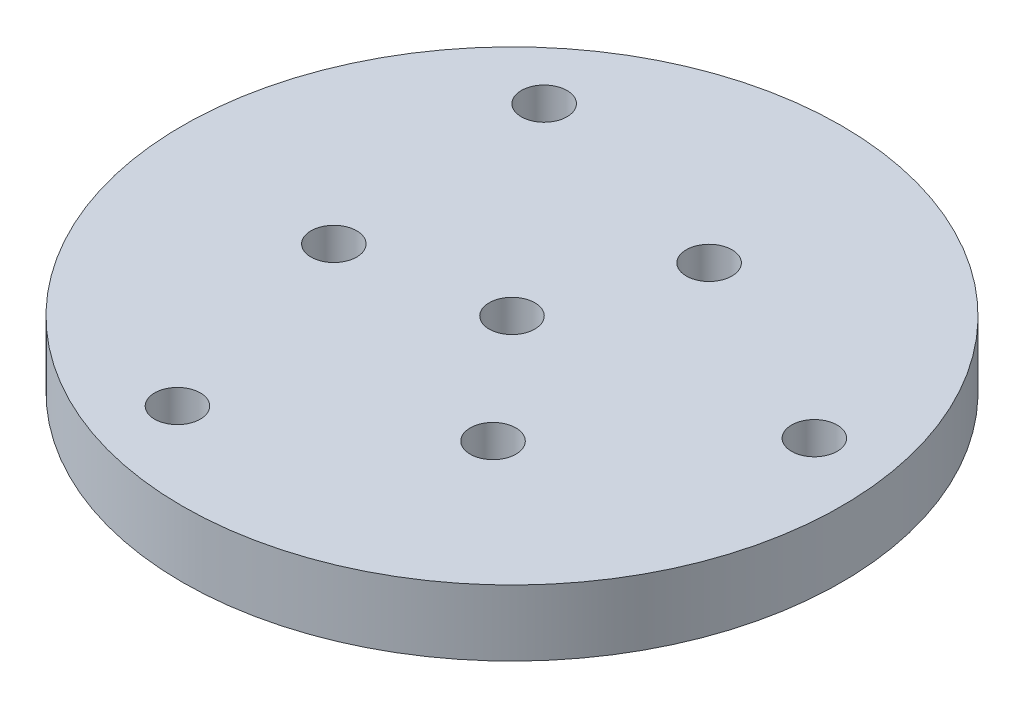
SolidWorks part; units mm, degrees
material "6061-T6 (SS)"
ref_plane "Front Plane" through (0, 0, 0) normal (0, 0, 1) x (1, 0, 0)
ref_plane "Top Plane" through (0, 0, 0) normal (0, 1, 0) x (1, 0, 0)
ref_plane "Right Plane" through (0, 0, 0) normal (1, 0, 0) x (0, 0, -1)
sketch "Sketch1" plane through (0, 0, 0) normal (0, 1, 0) x (1, 0, 0)
  circle A0 centre (0, 0) radius 47.625
  circle A1 centre (0, 0) radius 3.3
  circle A2 centre (0, 25.4) radius 1.5875 construction
  dimension "D1" = 95.25
  dimension "D2" = 6.6
  dimension "D3" = 3.175
  dimension "D4" = 25.4
extrude "Boss-Extrude1" add sketch "Sketch1" along normal mid plane 9.525
ref_plane "Plane1" through (0, 0, 50.8) normal (0, 0, 1) x (1, 0, 0)
sketch "Sketch2" plane through (0, 0, 50.8) normal (0, 0, 1) x (1, 0, 0)
  circle A0 centre (0, 0) radius 1.3526
  dimension "D1" = 2.7051
extrude "Cut-Extrude1" [suppressed] cut sketch "Sketch2" against normal blind 12.7
sketch "Sketch3" plane through (0, 0, 0) normal (0, 0, 1) x (1, 0, 0)
  line L0 (0, 4.7625) -> (0, -4.7625)
  line L1 (47.625, 4.7625) -> (-47.625, 4.7625) construction
  line L2 (-47.625, -4.7625) -> (47.625, -4.7625) construction
pattern_circular "CirPattern1" [suppressed] count 4 over 360 about axis through (0, 4.7625, 0) along (0, -1, 0) of bodies 102
sketch "Sketch4" plane through (0, 4.7625, 0) normal (0, 1, 0) x (1, 0, 0)
  line L0 (0, 0) -> (0, -35.975) construction
  line L1 (-12.9007, -35.4443) -> (0, 0) construction
  line L2 (0, 0) -> (14.286, -17.0253) construction
  circle A0 centre (-12.9007, -35.4443) radius 3.3
  circle A1 centre (-24.2453, 28.8944) radius 3.3
  circle A2 centre (37.146, 6.5498) radius 3.3
  circle A3 centre (14.286, -17.0253) radius 3.3
  circle A4 centre (-21.8874, -3.8593) radius 3.3
  circle A5 centre (7.6014, 20.8847) radius 3.3
  point P12 (0, 0)
  point P19 (0, 0)
  dimension "D1" = 6.6
  dimension "D7" = 6.6
  dimension "D2" = 37.719
  dimension "D3" = 20
  dimension "D5" = 60
  dimension "D6" = 22.225
  dimension "D4" = 3
  dimension "D8" = 3
extrude "Cut-Extrude2" cut sketch "Sketch4" against normal through all
equation "\"Body_Tube_OD\"= 4.024in"
equation "\"Body_Tube_ID\"= 3.90in"
equation "\"SS_Fwd_Bulkhead_OD\"=3.75"
equation "\"D1@Sketch1\"=\"SS_Fwd_Bulkhead_OD\""
equation "\"Bodytube_OD\" = 6.17in"
equation "\"Bodytube_ID\" = 5.998in"
equation "\"Motor_OD\" = 4in"
equation "\"Fwd_Tube_Length\" = 40in"
equation "\"Mid_Tube_Length\" = 1in"
equation "\"Mid_Coupler_Length\" = 13in"
equation "\"Aft_Section_Length\"= 39in"
equation "\"AB_Coupler_OD_Length\"= 1in"
equation "\"AB_Coupling_Section_Length\"= 0.375in"
equation "\"AB_Coupler_Length\"= \"AB_Coupler_OD_Length\" + \"AB_Coupling_Section_Length\" * 2"
equation "\"Cutout_Angle\" = 80"
equation "\"AB_Paddle_Height\" = 0.375in"
equation "\"AB_Coupler_Num_Screws\"= 6"
equation "\"AB_BKHD_Thickness\" = 0.375in"
equation "\"AB_Mount_From_Bottom\" = 23.175in"
equation "\"Num_Cutouts\" = 3"
equation "\"AB_Coupler_OD\"= 6.17in"
equation "\"AB_Coupler_ID\"= 5.75in"
equation "\"AB_Coupler_Surface_Diameter\"= 5.998in"
equation "\"AB_Coupling_Screw_Diameter\"= 0.1065in"
equation "\"AB_Central_Bushing_Length\" = .75in"
equation "\"Lead_Screw_Dist\" = 3.4in"
equation "\"Lead_Screw_Diam\" = 11mm"
equation "\"Lead_Screw_Length\" = (\"Mid_Coupler_Length\" + 2*0.375in + 2*0.5in)"
equation "\"Paddle_Pin_Offset\" = .25in"
equation "\"Paddle_Pin_Radius\" = 2.25in"
equation "\"SS_Paddle_Pin_Radius\" = 2.25*0.66in"
equation "\"Paddle_Gear_OD\" = 3.2in"
equation "\"Drive_Gear_OD\" = 1.7in"
equation "\"Fwd_BKHD_From_Top\" = 18in"
equation "\"Fin_Thickness\"= .118in"
equation "\"Guiderail_Cutout_Diameter\"= 1.5in"
equation "\"DB9_Hole_Dist\" = 25mm"
equation "\"DB9_Relief_Width\" = 0.47in"
equation "\"DB9_Relief_Hole_Offset\" = 0.09in"
equation "\"Airbrakes_Wire_Hole_Dia\" = .25in"
equation "\"Airbrakes_Wire_Hole_Dist\" = 1.1in"
equation "\"Servo_Gear_Offset\" = 0.5in"
